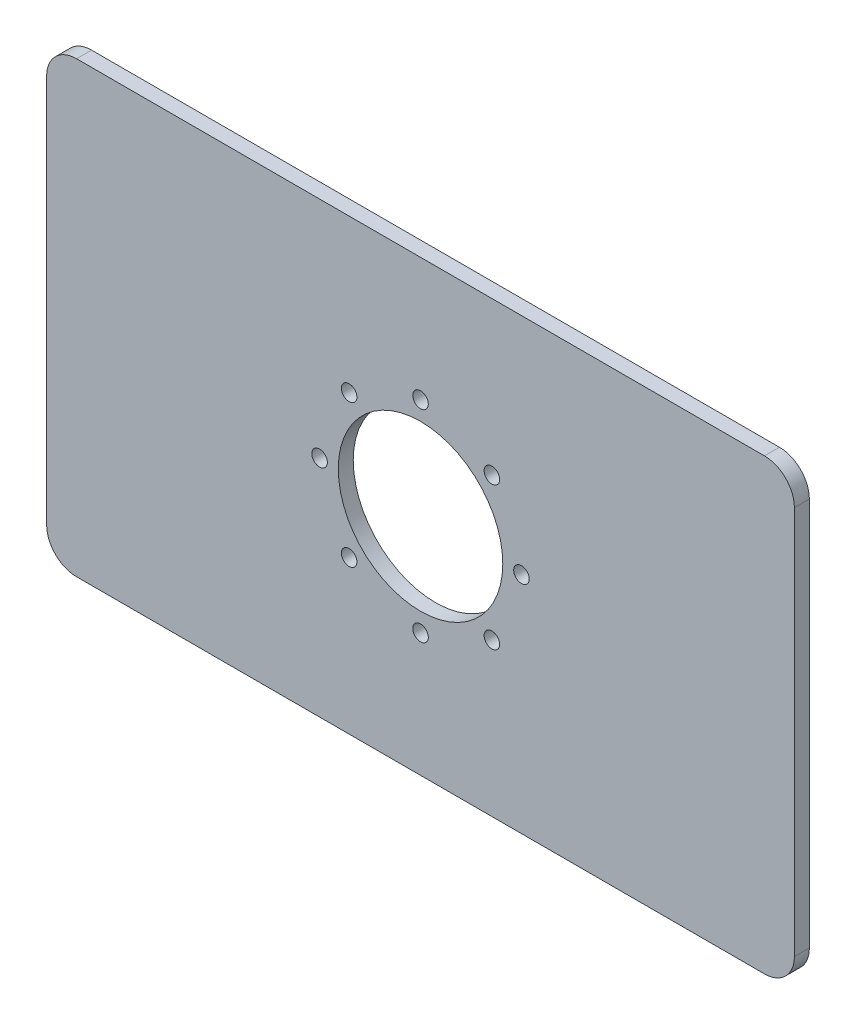
SolidWorks part; units mm, degrees
material "默认 (3)"
ref_plane "前视基准面" through (0, 0, 0) normal (0, 0, 1) x (1, 0, 0)
ref_plane "上视基准面" through (0, 0, 0) normal (0, 1, 0) x (1, 0, 0)
ref_plane "右视基准面" through (0, 0, 0) normal (1, 0, 0) x (0, 0, -1)
other "Configuration Table"
sketch "草图1" plane through (0, 0, 0) normal (0, 0, 1) x (1, 0, 0)
  line L1 (-125, 75) -> (125, 75)
  line L2 (-125, 75) -> (-125, -75)
  line L3 (-125, -75) -> (125, -75)
  line L4 (125, 75) -> (125, -75)
  line L5 (-125, 75) -> (125, -75) construction
  line L6 (-125, -75) -> (125, 75) construction
  point P0 (0, 0)
  dimension "D1" = 150
  dimension "D2" = 250
extrude "凸台-拉伸1" add sketch "草图1" along normal blind 5
sketch "草图5" plane through (0, 0, 0) normal (0, 0, -1) x (-1, 0, 0)
  circle A1 centre (0, 0) radius 27.5
  circle A2 centre (0, 0) radius 27.5
  circle A3 centre (23.8649, 23.8649) radius 2.6
  circle A4 centre (23.8649, 23.8649) radius 2.6
  circle A5 centre (0, 33.75) radius 2.6
  circle A6 centre (0, 33.75) radius 2.6
  circle A7 centre (-23.8649, 23.8649) radius 2.6
  circle A8 centre (-23.8649, 23.8649) radius 2.6
  circle A9 centre (-33.75, 0) radius 2.6
  circle A10 centre (-33.75, 0) radius 2.6
  circle A11 centre (-23.8649, -23.8649) radius 2.6
  circle A12 centre (-23.8649, -23.8649) radius 2.6
  circle A13 centre (0, -33.75) radius 2.6
  circle A14 centre (0, -33.75) radius 2.6
  circle A15 centre (23.8649, -23.8649) radius 2.6
  circle A16 centre (23.8649, -23.8649) radius 2.6
  circle A17 centre (33.75, 0) radius 2.6
  circle A18 centre (33.75, 0) radius 2.6
  dimension "D1" = 0
  dimension "D2" = 0
  dimension "D3" = 0
  dimension "D4" = 0
  dimension "D5" = 0
  dimension "D6" = 0
  dimension "D7" = 0
  dimension "D8" = 0
  dimension "D9" = 0
extrude "切除-拉伸2" cut sketch "草图5" against normal up to next
fillet "圆角1" radius 10 4 edges at (125, 75, 2.5) (125, -75, 2.5) (-125, -75, 2.5) (-125, 75, 2.5)
